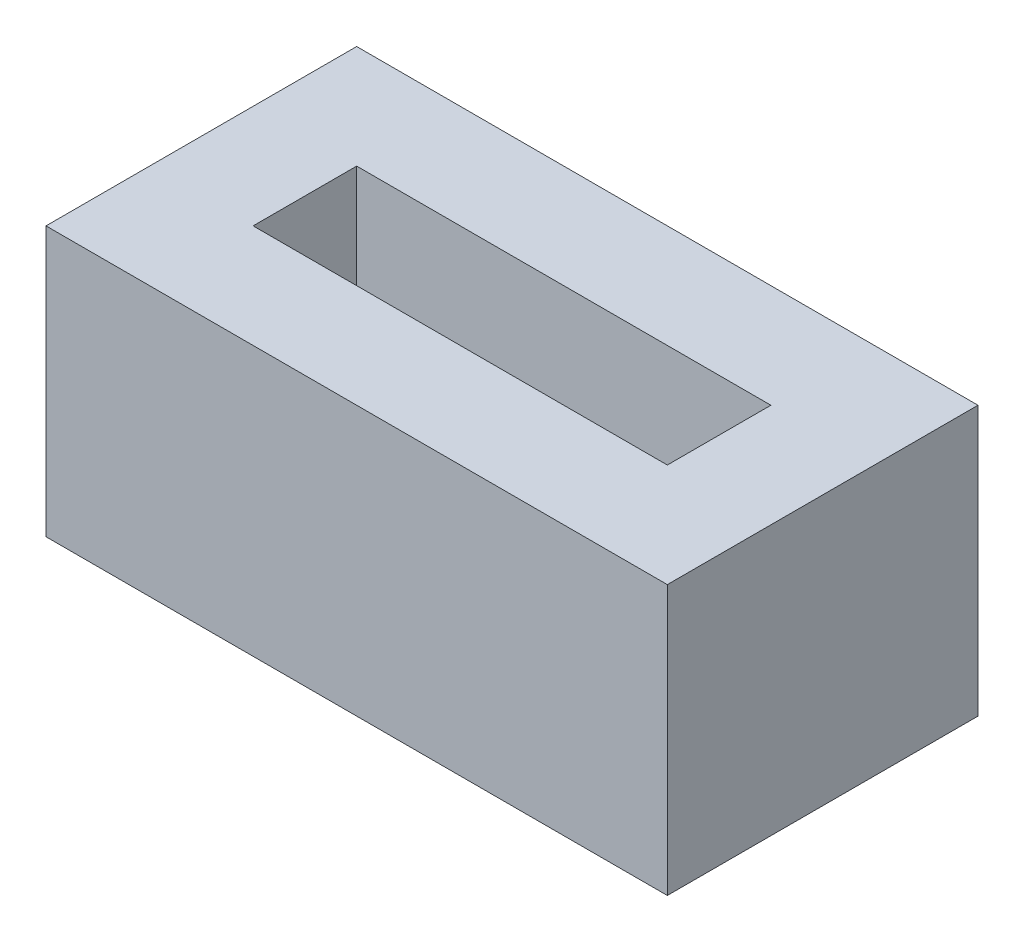
SolidWorks part; units mm, degrees
ref_plane "Front Plane" through (0, 0, 0) normal (0, 0, 1) x (1, 0, 0)
ref_plane "Top Plane" through (0, 0, 0) normal (0, 1, 0) x (1, 0, 0)
ref_plane "Right Plane" through (0, 0, 0) normal (1, 0, 0) x (0, 0, -1)
sketch "Sketch1" plane through (0, 0, 0) normal (0, 1, 0) x (1, 0, 0)
  line L1 (-19.05, -9.525) -> (19.05, -9.525)
  line L2 (-19.05, -9.525) -> (-19.05, 9.525)
  line L3 (-19.05, 9.525) -> (19.05, 9.525)
  line L4 (19.05, -9.525) -> (19.05, 9.525)
  line L5 (-19.05, -9.525) -> (19.05, 9.525) construction
  line L6 (-19.05, 9.525) -> (19.05, -9.525) construction
  point P0 (0, 0)
  dimension "D1" = 19.05
  dimension "D2" = 38.1
extrude "Boss-Extrude1" add sketch "Sketch1" along normal blind 16.51
sketch "Sketch2" plane through (0, 16.51, 0) normal (0, 1, 0) x (1, 0, 0)
  line L1 (-12.7, -3.175) -> (12.7, -3.175)
  line L2 (-12.7, -3.175) -> (-12.7, 3.175)
  line L3 (-12.7, 3.175) -> (12.7, 3.175)
  line L4 (12.7, -3.175) -> (12.7, 3.175)
  line L5 (-12.7, -3.175) -> (12.7, 3.175) construction
  line L6 (-12.7, 3.175) -> (12.7, -3.175) construction
  point P0 (0, 0)
  dimension "D1" = 6.35
  dimension "D2" = 25.4
extrude "Cut-Extrude1" cut sketch "Sketch2" against normal blind 12.7
